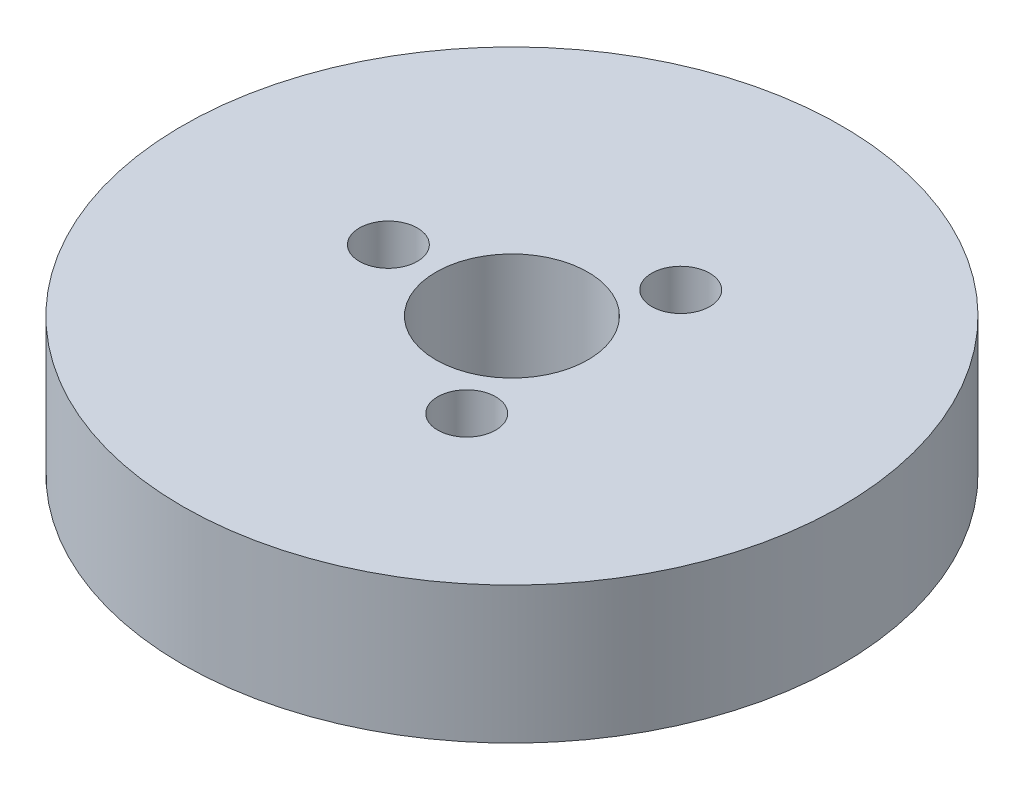
SolidWorks part; units mm, degrees
ref_plane "Front Plane" through (0, 0, 0) normal (0, 0, 1) x (1, 0, 0)
ref_plane "Top Plane" through (0, 0, 0) normal (0, 1, 0) x (1, 0, 0)
ref_plane "Right Plane" through (0, 0, 0) normal (1, 0, 0) x (0, 0, -1)
sketch "Sketch1" plane through (0, 0, 0) normal (0, 1, 0) x (1, 0, 0)
  circle A0 centre (0, 0) radius 65
  dimension "FLANGE_OD" = 130
extrude "Boss-Extrude1" add sketch "Sketch1" along normal blind 27
sketch "Sketch2" plane through (0, 0, 0) normal (0, 1, 0) x (1, 0, 0)
  circle A0 centre (0, 0) radius 15
  dimension "BORE_D" = 30
extrude "Cut-Extrude1" cut sketch "Sketch2" along normal through all
sketch "Sketch3" plane through (0, 27, 0) normal (0, 1, 0) x (1, 0, 0)
  circle A0 centre (0, 0) radius 24.3696 construction
  circle A1 centre (-24.3696, 0) radius 5.718
  dimension "BOLT_D" = 11.4361
  dimension "BOLT_PCD" = 48.7392
extrude "Cut-Extrude2" cut sketch "Sketch3" against normal blind 22.7378
pattern_circular "CirPattern1" count 3 over 360 about axis through (0, 0, 0) along (0, 1, 0) of "Cut-Extrude2"
